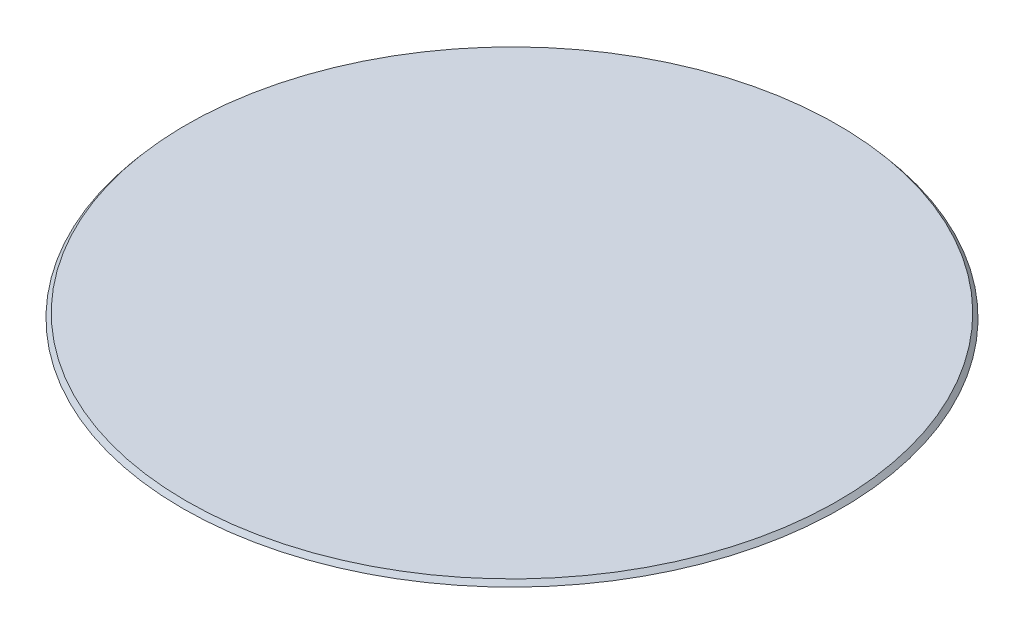
SolidWorks part; units mm, degrees
ref_plane "Front" through (0, 0, 0) normal (0, 0, 1) x (1, 0, 0)
ref_plane "Top" through (0, 0, 0) normal (0, 1, 0) x (1, 0, 0)
ref_plane "Right" through (0, 0, 0) normal (1, 0, 0) x (0, 0, -1)
ref_axis "Axis1" through (-84.4107, 0, 0) along (1, 0, 0)
ref_axis "Axis2" through (0, 64.3378, 0) along (0, -1, 0)
ref_axis "Axis3" through (0, 0, -102.329) along (0, 0, 1)
sketch "Sketch1" plane through (0, 0, 0) normal (1, 0, 0) x (0, 0, -1)
  line L0 (0, 0) -> (29.1644, 0)
  line L1 (29.1644, 0) -> (29.5, -0.4)
  line L2 (29.5, -0.4) -> (26.2, -1.9)
  line L3 (26.2, -1.9) -> (26.2, -0.9)
  line L4 (26.2, -0.9) -> (22.1, -0.9)
  line L5 (22.1, -0.9) -> (22.1, -1.9)
  line L6 (22.1, -1.9) -> (0, -1.9)
  line L9 (0, -1.9) -> (0, 0)
  line L10 (0, 50) -> (0, -50) construction
  dimension "D1" = 29.5
  dimension "D2" = 0.4
  dimension "D3" = 26.2
  dimension "D4" = 1
  dimension "D5" = 1.5
  dimension "D6" = 4.1
  dimension "D7" = 1
  dimension "D11" = 40
revolve "Revolve1" add sketch "Sketch1" angle 360 about axis through (0, 64.3378, 0) along (0, -1, 0)
sketch "Sketch2" plane through (0, -1.9, 0) normal (0, -1, 0) x (1, 0, 0)
  line L0 (9.35, 18.2436) -> (3.85, 13.0339)
  line L1 (-3.85, 13.0339) -> (-9.35, 18.2436)
  arc A0 (-9.35, 18.2436) -> (9.35, 18.2436) centre (0, 0) cw
  arc A1 (3.85, 13.0339) -> (-3.85, 13.0339) centre (0, 17.0985) cw
  circle A3 centre (0, 0) radius 26.2 construction
  point P6 (0, 20.5)
  point P10 (0, 11.5)
  dimension "D1" = 5.7
  dimension "D2" = 9
  dimension "D3" = 18.7
  dimension "D4" = 7.7
extrude "Boss-Extrude1" add sketch "Sketch2" along normal blind 4
pattern_circular "CirPattern1" count 5 over 360 about axis through (0, 64.3378, 0) along (0, -1, 0) of "Boss-Extrude1"
